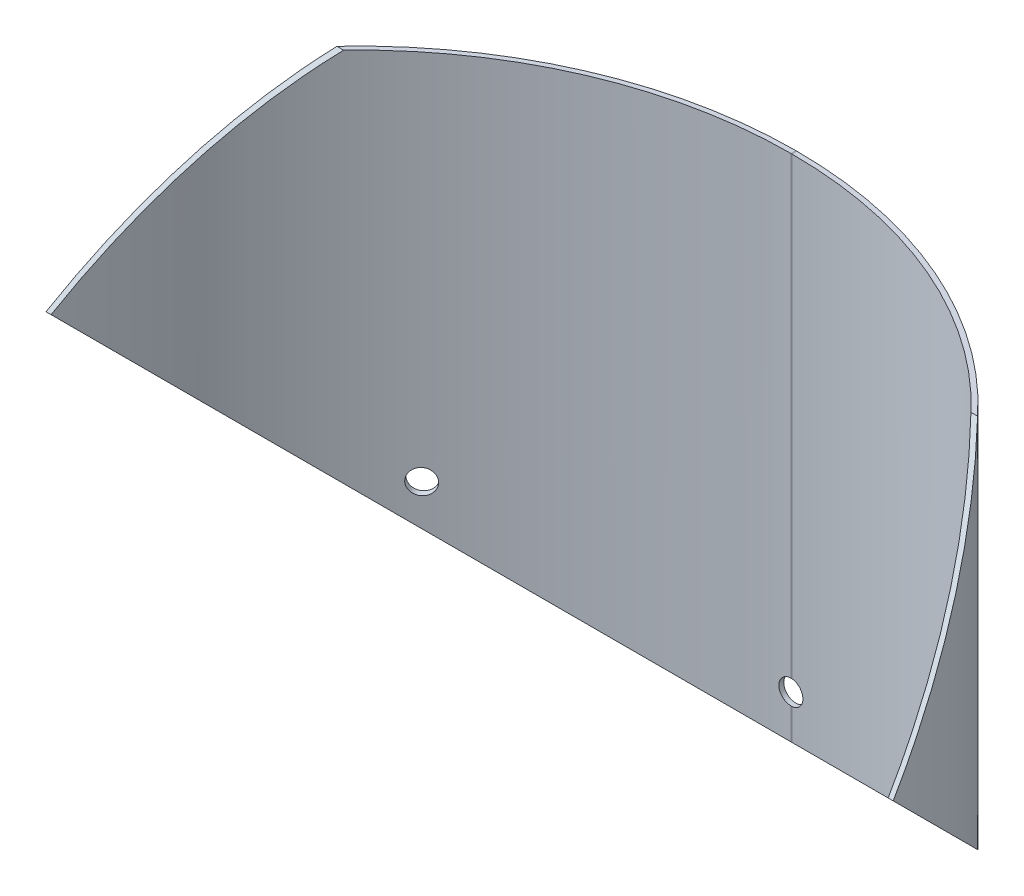
SolidWorks part; units mm, degrees
note: The reader was unsure of these and kept them because the rebuilt part matched: flange length of "Edge-Flange1".
ref_plane "Front Plane" through (0, 0, 0) normal (0, 0, 1) x (1, 0, 0)
ref_plane "Top Plane" through (0, 0, 0) normal (0, 1, 0) x (1, 0, 0)
ref_plane "Right Plane" through (0, 0, 0) normal (1, 0, 0) x (0, 0, -1)
sketch "Sketch1" plane through (0, 0, 0) normal (0, 0, 1) x (1, 0, 0)
  line L0 (-0.127, 152.4) -> (-0.127, 0)
  line L1 (-0.127, 152.4) -> (0.127, 152.4)
  line L2 (-0.127, 0) -> (0.127, 0)
  line L3 (0.127, 152.4) -> (0.127, 0)
  dimension "D1" = 0.254
  dimension "D2" = 152.4
base flange "Base-Flange1" sketch "Sketch1" thickness 1.2903 reverse thickness direction no parameters "D1"=76.2
edge flange "Edge-Flange1" sketch "Sketch10" flange profiles "Sketch10", "Sketch11" flange angle 90 flange length 127 flange position bend outside bend radius 114.3 thickness 1.2903 parameters "D6"=10, "D8"=0.254
sketch "Sketch10" plane through (0.127, 0, 0) normal (1, 0, 0) x (0, 1, 0)
  line L0 (0, 0) -> (152.4, 0) construction
  line L1 (0, 0) -> (152.4, 0)
  line L2 (0, 0) -> (0, 125.7097)
  line L3 (0, 125.7097) -> (152.4, 125.7097)
  line L4 (152.4, 125.7097) -> (152.4, 0)
sketch "Sketch11" plane through (-0.127, 0, 0) normal (-1, 0, 0) x (0, -1, 0)
  line L0 (-152.4, 0) -> (0, 0) construction
  line L1 (-152.4, 0) -> (0, 0)
  line L2 (-152.4, 0) -> (-152.4, 125.7097)
  line L3 (-152.4, 125.7097) -> (0, 125.7097)
  line L4 (0, 125.7097) -> (0, 0)
bend "EdgeBend1" bend radius 114.3 bend angle 90 parameters "D5"=1
bend "EdgeBend2" bend radius 114.3 bend angle 90 parameters "D5"=2
sketch "Sketch14" plane through (0, 0, 0) normal (1, 0, 0) x (0, 0, -1)
  line L0 (-85.0863, 102.7898) -> (40.6919, -22.9884)
  line L1 (-142.9844, 160.6878) -> (-256.1141, 47.5581)
  line L2 (40.6919, -22.9884) -> (-72.4379, -136.1182)
  line L3 (-256.1141, 47.5581) -> (-72.4379, -136.1182)
  line L4 (1.2903, 0) -> (1.2903, 152.4) construction
  line L5 (-85.0863, 102.7898) -> (-6.6808, 181.1953)
  line L6 (-6.6808, 181.1953) -> (-68.7594, 243.2738)
  line L7 (-68.7594, 243.2738) -> (-142.9844, 160.6878)
  dimension "D1" = 45
extrude "Cut-Extrude6" cut sketch "Sketch14" against normal through all both and the other way through all
sketch "Sketch15" plane through (0, 0, -1.2903) normal (0, 0, -1) x (-1, 0, 0)
  line L0 (0.127, 152.4) -> (0.127, 16.4131) construction
  circle A0 centre (0.127, 29.1131) radius 3.175
  dimension "D1" = 6.35
  dimension "D2" = 12.7
extrude "Cut-Extrude7" cut sketch "Sketch15" against normal through all both and the other way through all
ref_plane "Plane2" through (0, 7.0557, -7.0557) normal (0, -0.7071, 0.7071) x (1, 0, 0)
ref_plane "Plane3" through (0, 95.7341, 95.7341) normal (0, 0.7071, 0.7071) x (1, 0, 0)
ref_plane "Plane4" through (0, 79.5696, 79.5696) normal (0, 0.7071, 0.7071) x (1, 0, 0)
sketch "Sketch17" plane through (0, 79.5696, 79.5696) normal (0, 0.7071, 0.7071) x (1, 0, 0)
  line L0 (0, 0) -> (0, 83.6506) construction
pattern_circular "CirPattern2" count 2 every 52 about axis through (0, 79.5696, 79.5696) along (0, 0.7071, -0.7071) of "Cut-Extrude7"
sketch "Bend-Lines1" [suppressed] plane through (0, 0, 0) normal (0, 1, 0) x (1, 0, 0)
sketch "Bounding-Box1" [suppressed] plane through (0, 0, 0) normal (0, 1, 0) x (1, 0, 0)
sheet metal parameters "Sheet-Metal1" thickness 1.2903 parameters "D1"=76.2
flat pattern "Flat-Pattern1" [suppressed]
sketch "Bend-Lines2" plane through (0, 0, 0) normal (0, 1, 0) x (1, 0, 0)
sketch3d "Bounding-Box2" [suppressed]
  line L0 (-0.254, 152.4, 0) -> (-0.254, 0, 0) construction
  line L1 (0, 152.4, 0) -> (0, 0, 0) construction
  line L2 (-0.254, 152.4, 0) -> (0, 152.4, 0) construction
  line L3 (-0.254, 0, 0) -> (0, 0, 0) construction
sheet metal parameters "Sheet-Metal2" thickness 1.2903 parameters "D1"=76.2
flat pattern "Flat-Pattern1"
sketch "Bend-Lines2" plane through (0, 0, 0) normal (0, 0, 1) x (1, 0, 0)
  line L0 (-90.4047, 152.4) -> (-90.4047, 0) construction
  line L1 (90.4047, 0) -> (90.4047, 152.4) construction
  line L2 (-90.4047, 152.4) -> (-90.4047, 0) construction
  line L3 (90.4047, 0) -> (90.4047, 152.4) construction
sketch3d "Bounding-Box2" [suppressed]
  line L0 (-192.0921, 0, 0) -> (192.0921, 0, 0) construction
  line L1 (-192.0921, 152.4, 0) -> (192.0921, 152.4, 0) construction
  line L2 (-192.0921, 0, 0) -> (-192.0921, 152.4, 0) construction
  line L3 (192.0921, 0, 0) -> (192.0921, 152.4, 0) construction
bend of the flat pattern "Flatten-<EdgeBend1>1"
bend of the flat pattern "Flatten-<EdgeBend2>1"
sheet metal parameters "Sheet-Metal5" thickness 1.2903 parameters "D1"=76.2
flat pattern "Flat-Pattern1"
sketch "Bend-Lines2" plane through (0, 0, 0) normal (0, 0, 1) x (1, 0, 0)
  line L0 (-90.4047, 152.4) -> (-90.4047, 41.8428) construction
  line L1 (90.4047, 40.977) -> (90.4047, 152.4) construction
  line L2 (-90.4047, 152.4) -> (-90.4047, 41.8428) construction
  line L3 (90.4047, 40.977) -> (90.4047, 152.4) construction
sketch3d "Bounding-Box2" [suppressed]
  line L0 (-192.0921, 2.1994, 0) -> (192.0921, 2.1994, 0) construction
  line L1 (-192.0921, 152.4, 0) -> (192.0921, 152.4, 0) construction
  line L2 (-192.0921, 2.1994, 0) -> (-192.0921, 152.4, 0) construction
  line L3 (192.0921, 2.1994, 0) -> (192.0921, 152.4, 0) construction
bend of the flat pattern "Flatten-<EdgeBend1>1"
bend of the flat pattern "Flatten-<EdgeBend2>1"
sheet metal parameters "Sheet-Metal6" thickness 1.2903 parameters "D1"=76.2
flat pattern "Flat-Pattern1"
sketch "Bend-Lines2" plane through (0, 0, 0) normal (0, 0, 1) x (1, 0, 0)
  line L0 (-75.6359, 40.9808) -> (-75.6359, 152.4) construction
  line L1 (75.6359, 152.4) -> (75.6359, 40.9808) construction
  line L2 (-75.6359, 40.9808) -> (-75.6359, 152.4) construction
  line L3 (75.6359, 152.4) -> (75.6359, 40.9808) construction
sketch3d "Bounding-Box2" [suppressed]
  line L0 (-151.1448, 17.0583, 0) -> (151.1448, 17.0583, 0) construction
  line L1 (-151.1448, 152.4, 0) -> (151.1448, 152.4, 0) construction
  line L2 (-151.1448, 17.0583, 0) -> (-151.1448, 152.4, 0) construction
  line L3 (151.1448, 17.0583, 0) -> (151.1448, 152.4, 0) construction
bend of the flat pattern "Flatten-<EdgeBend1>1"
bend of the flat pattern "Flatten-<EdgeBend2>1"
sheet metal parameters "Sheet-Metal8" thickness 1.2903 parameters "D1"=76.2
flat pattern "Flat-Pattern1"
sketch "Bend-Lines2" plane through (0, 0, 0) normal (0, 0, 1) x (1, 0, 0)
  line L0 (-75.6359, 40.9808) -> (-75.6359, 52.6887) construction
  line L1 (75.6359, 152.4) -> (75.6359, 55.7139) construction
  line L2 (-75.6359, 40.9808) -> (-75.6359, 52.6887) construction
  line L3 (75.6359, 152.4) -> (75.6359, 55.7139) construction
  line L4 (-75.6359, 55.4837) -> (-75.6359, 152.4) construction
  line L5 (75.6359, 52.164) -> (75.6359, 40.9808) construction
sketch3d "Bounding-Box2" [suppressed]
  line L0 (-151.1448, 17.0583, 0) -> (151.1448, 17.0583, 0) construction
  line L1 (-151.1448, 152.4, 0) -> (151.1448, 152.4, 0) construction
  line L2 (-151.1448, 17.0583, 0) -> (-151.1448, 152.4, 0) construction
  line L3 (151.1448, 17.0583, 0) -> (151.1448, 152.4, 0) construction
bend of the flat pattern "Flatten-<EdgeBend1>1"
bend of the flat pattern "Flatten-<EdgeBend2>1"
